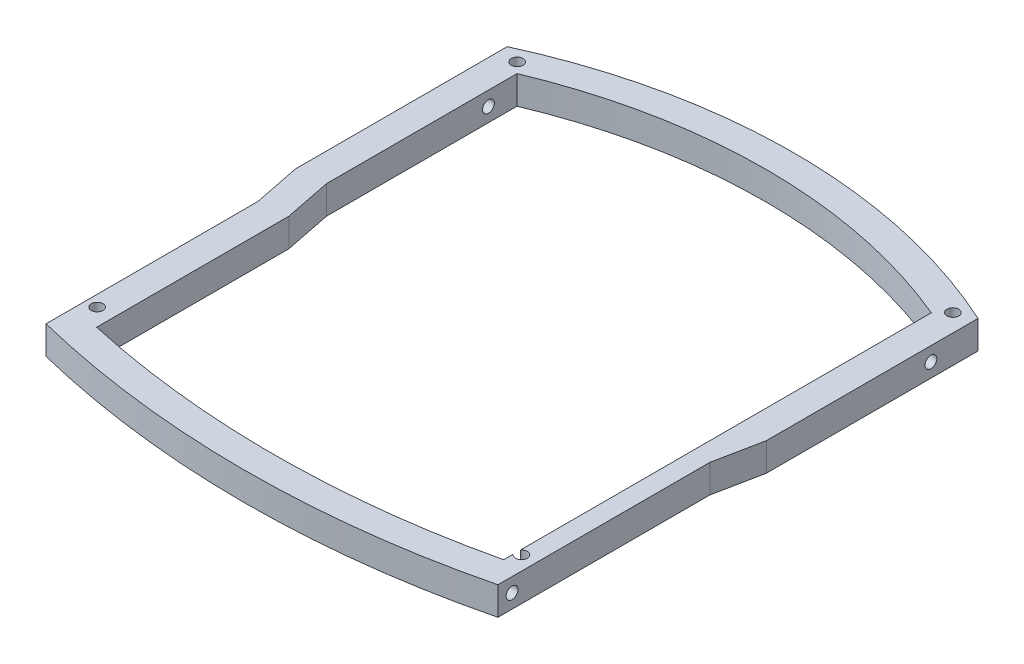
SolidWorks part; units mm, degrees
ref_plane "Front Plane" through (0, 0, 0) normal (0, 0, 1) x (1, 0, 0)
ref_plane "Top Plane" through (0, 0, 0) normal (0, 1, 0) x (1, 0, 0)
ref_plane "Right Plane" through (0, 0, 0) normal (1, 0, 0) x (0, 0, -1)
sketch "Sketch1" plane through (0, 0, 0) normal (0, 1, 0) x (1, 0, 0)
  line L0 (-50, 5) -> (-50, 49.98)
  line L1 (50, 49.98) -> (50, 5)
  line L2 (-48, -50) -> (-48, -5)
  line L3 (-48, -5) -> (-50, 5)
  line L4 (48, -50) -> (48, -5)
  line L5 (48, -5) -> (50, 5)
  line L6 (-44, 5.5941) -> (-44, 46.0594)
  line L7 (44, 46.0594) -> (44, 5.5941)
  line L8 (42, -4.4059) -> (44, 5.5941)
  line L9 (42, -45.2445) -> (42, -4.4059)
  line L10 (-42, -45.2445) -> (-42, -4.4059)
  line L11 (-42, -4.4059) -> (-44, 5.5941)
  arc A0 (-50, 49.98) -> (50, 49.98) centre (0, -59.1071) cw
  arc A1 (48, -50) -> (-48, -50) centre (0, 144.1546) cw
  arc A2 (-44, 46.0594) -> (44, 46.0594) centre (0, -59.1071) cw
  arc A3 (42, -45.2445) -> (-42, -45.2445) centre (0, 144.1546) cw
  dimension "D1" = 120
  dimension "D11" = 200
  dimension "D2" = 100
  dimension "D3" = 100
  dimension "D5" = 50
  dimension "D6" = 50
  dimension "D4" = 2
  dimension "D7" = 2
  dimension "D8" = 10
  dimension "D9" = 5
  dimension "D10" = 6
extrude "Boss-Extrude1" add sketch "Sketch1" along normal blind 6
hole_wizard "Tap Drill for M3 Tap1" positions "Sketch3" profile "Sketch2" hole size "M3" standard "ISO"
sketch "Sketch3" plane through (50, 0, 0) normal (1, 0, 0) x (0, 0, -1)
  line L1 (5, 6) -> (49.98, 6) construction
  line L3 (-50, 6) -> (-50, 0) construction
  line L4 (49.98, 6) -> (49.98, 0) construction
  point P0 (-47, 3)
  point P11 (39.98, 3)
  dimension "D1" = 3
  dimension "D2" = 3
  dimension "D3" = 10
sketch "Sketch2" plane through (50, 3, 47) normal (0, 1, 0) x (0, 0, -1)
  line L0 (0, 0) -> (0, 10.7511)
  line L1 (0, 10.7511) -> (1.25, 10)
  line L2 (1.25, 10) -> (1.25, 0)
  line L5 (1.25, 0) -> (0, 0)
  line L10 (0, 10.7511) -> (-1.25, 10) construction
  line L11 (0, -6.35) -> (0, 107.95) construction
  dimension "Hole Dia." = 2.5
  dimension "Hole Depth" = 10
  dimension "Drill Angle" = 118
sketch "Sketch4" plane through (0, 6, 0) normal (0, 1, 0) x (1, 0, 0)
  line L0 (44, 5.5941) -> (44, -44.7899)
  line L1 (44, 5.5941) -> (42, -4.4059)
  line L2 (42, -4.4059) -> (42, -45.2445)
  arc A0 (42, -45.2445) -> (44, -44.7899) centre (0, 144.1546) ccw
  arc A1 (-42, -45.2445) -> (42, -45.2445) centre (0, 144.1546) ccw construction
extrude "Cut-Extrude1" cut sketch "Sketch4" against normal up to next
mirror "Mirror3" about plane through (0, 0, 0) normal (1, 0, 0) of "Tap Drill for M3 Tap1"
hole_wizard "Tap Drill for M3 Tap2" positions "Sketch6" profile "Sketch5" hole size "M3" standard "ISO"
sketch "Sketch6" plane through (0, 6, 0) normal (0, 1, 0) x (1, 0, 0)
  line L2 (50, 5) -> (50, 49.98) construction
  line L3 (-50, 49.98) -> (-50, 5) construction
  point P0 (45, -42)
  point P2 (-45.65, -41.5)
  point P4 (-46.15, 48.23)
  point P6 (46.25, 48.4)
  dimension "D1" = 5
  dimension "D2" = 8
  dimension "D3" = 1.58
  dimension "D4" = 3.75
  dimension "D5" = 3.85
  dimension "D6" = 1.75
  dimension "D7" = 4.35
  dimension "D8" = 8.5
sketch "Sketch5" plane through (45, 6, 42) normal (1, 0, 0) x (0, 0, 1)
  line L0 (0, 0) -> (0, 10.7511)
  line L1 (0, 10.7511) -> (1.25, 10)
  line L2 (1.25, 10) -> (1.25, 0)
  line L5 (1.25, 0) -> (0, 0)
  line L10 (0, 10.7511) -> (-1.25, 10) construction
  line L11 (0, -6.35) -> (0, 107.95) construction
  dimension "Hole Dia." = 2.5
  dimension "Hole Depth" = 10
  dimension "Drill Angle" = 118
